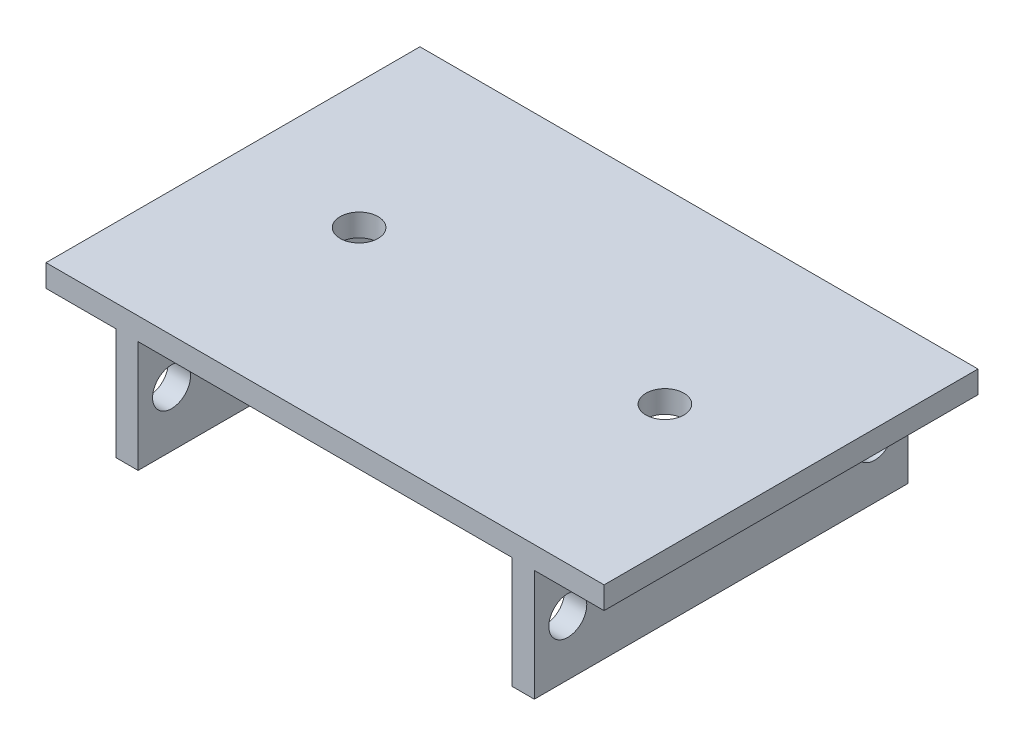
SolidWorks part; units mm, degrees
ref_plane "Front Plane" through (0, 0, 0) normal (0, 0, 1) x (1, 0, 0)
ref_plane "Top Plane" through (0, 0, 0) normal (0, 1, 0) x (1, 0, 0)
ref_plane "Right Plane" through (0, 0, 0) normal (1, 0, 0) x (0, 0, -1)
sketch "Sketch1" plane through (0, 0, 0) normal (0, 1, 0) x (1, 0, 0)
  line L1 (-72.1861, 30.4945) -> (-22.1861, 30.4945)
  line L2 (-72.1861, 30.4945) -> (-72.1861, -3.0055)
  line L3 (-72.1861, -3.0055) -> (-22.1861, -3.0055)
  line L4 (-22.1861, 30.4945) -> (-22.1861, -3.0055)
  dimension "D1" = 50
  dimension "D2" = 33.5
extrude "Boss-Extrude1" add sketch "Sketch1" along normal blind 2
sketch "Sketch6" plane through (0, 0, 0) normal (0, 1, 0) x (1, 0, 0)
  line L0 (-72.1861, -3.0055) -> (-22.1861, -3.0055) construction
  line L1 (-65.9361, -3.0055) -> (-63.9361, -3.0055)
  line L2 (-65.9361, -3.0055) -> (-65.9361, 30.4945)
  line L3 (-65.9361, 30.4945) -> (-63.9361, 30.4945)
  line L4 (-63.9361, -3.0055) -> (-63.9361, 30.4945)
  line L5 (-22.1861, 30.4945) -> (-72.1861, 30.4945) construction
  line L7 (-28.4361, -3.0055) -> (-30.4361, -3.0055)
  line L8 (-28.4361, -3.0055) -> (-28.4361, 30.4945)
  line L9 (-28.4361, 30.4945) -> (-30.4361, 30.4945)
  line L10 (-30.4361, -3.0055) -> (-30.4361, 30.4945)
  line L11 (-47.1861, 30.4945) -> (-47.1861, -3.0055) construction
  line L12 (-22.1861, 30.4945) -> (-72.1861, 30.4945) construction
  line L13 (-72.1861, -3.0055) -> (-22.1861, -3.0055) construction
  dimension "D1" = 33.5
  dimension "D3" = 2
extrude "Boss-Extrude2" add sketch "Sketch6" against normal blind 10
hole_wizard "M3 Clearance Hole3" positions "3DSketch2" profile "Sketch11" hole size "M3" standard "ANSI Metric"
sketch3d "3DSketch2"
  line L0 (-65.9361, -10, -30.4945) -> (-65.9361, 0, -30.4945) construction
  line L1 (-65.9361, -10, -30.4945) -> (-65.9361, -10, 3.0055) construction
  point P0 (-65.9361, -5, -27.4945)
  point P2 (-65.9361, -5, 0.0055)
  point P4 (-28.4361, -5, -27.4945)
  point P6 (-28.4361, -5, 0.0055)
  point P9 (0, 0, 0)
  point P10 (0, 0, 0)
  point P11 (0, 0, 0)
  point P12 (0, 0, 0)
  dimension "D1" = 3
  dimension "D2" = 5
  dimension "D3" = 27.5
sketch "Sketch11" plane through (-65.9361, -5, -27.4945) normal (0, 1, 0) x (0, 0, 1)
  line L0 (0, 0) -> (0, 11.0215)
  line L1 (0, 11.0215) -> (1.7, 10)
  line L2 (1.7, 10) -> (1.7, 0)
  line L5 (1.7, 0) -> (0, 0)
  line L10 (0, 11.0215) -> (-1.7, 10) construction
  line L11 (0, -6.35) -> (0, 107.95) construction
  dimension "Hole Dia." = 3.4
  dimension "Hole Depth" = 10
  dimension "Drill Angle" = 118
hole_wizard "M3 Clearance Hole4" positions "Sketch12" profile "Sketch13" hole size "M3" standard "ANSI Metric" end condition through all
sketch "Sketch12" plane through (0, 0, 0) normal (0, -1, 0) x (-1, 0, 0)
  line L0 (63.9361, -3.0055) -> (30.4361, -3.0055) construction
  line L1 (47.1861, 30.4945) -> (47.1861, -3.0055) construction
  line L2 (30.4361, 30.4945) -> (63.9361, 30.4945) construction
  point P0 (33.4861, 13.7445)
  point P15 (60.8861, 13.7445)
  dimension "D1" = 16.75
  dimension "D2" = 13.7
sketch "Sketch13" plane through (-33.4861, 0, -13.7445) normal (1, 0, 0) x (0, 0, -1)
  line L0 (0, 0) -> (0, 2)
  line L1 (0, 2) -> (1.7, 2)
  line L2 (1.7, 2) -> (1.7, 0)
  line L5 (1.7, 0) -> (0, 0)
  line L11 (0, -6.35) -> (0, 107.95) construction
  dimension "Thru Hole Dia." = 3.4
  dimension "Thru Hole Depth" = 2
